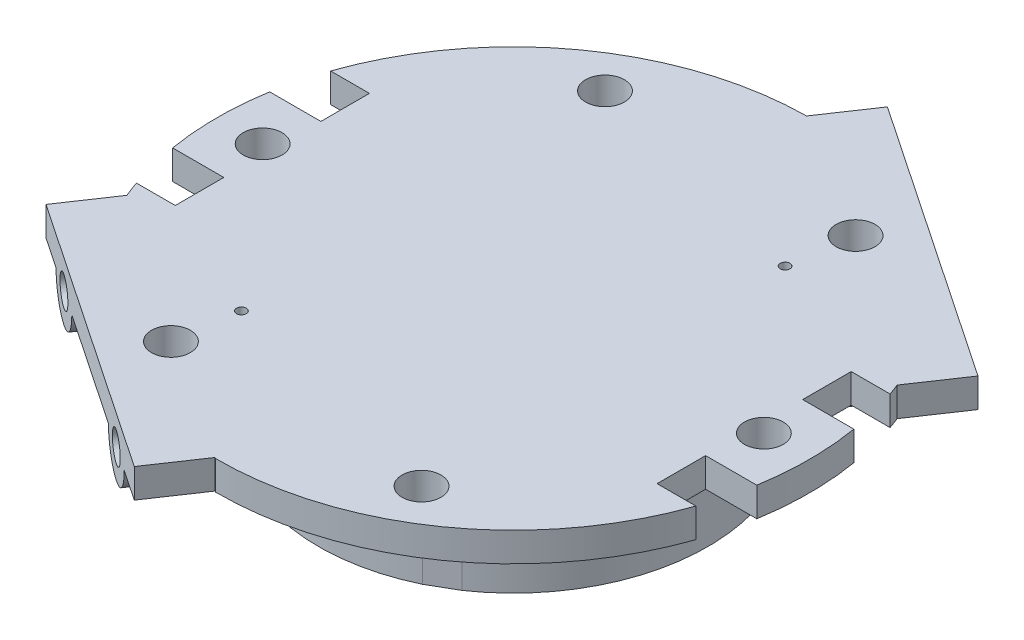
SolidWorks part; units mm, degrees
ref_plane "Alzado" through (0, 0, 0) normal (0, 0, 1) x (1, 0, 0)
ref_plane "Planta" through (0, 0, 0) normal (0, 1, 0) x (1, 0, 0)
ref_plane "Vista lateral" through (0, 0, 0) normal (1, 0, 0) x (0, 0, -1)
sketch "Croquis1" plane through (0, 0, 0) normal (0, 1, 0) x (1, 0, 0)
  circle A0 centre (0, 0) radius 30.5
extrude "Saliente-Extruir1" add sketch "Croquis1" along normal blind 3
sketch "Croquis5" plane through (0, 3, 0) normal (0, 1, 0) x (1, 0, 0)
  line L1 (28.8141, -5) -> (30.0874, -5)
  line L2 (28.8141, 5) -> (30.0874, 5)
  line L3 (-24.8141, 10) -> (-28.8141, 10)
  line L4 (24.8141, -5) -> (24.8141, -10)
  line L5 (-24.8141, -10) -> (-28.8141, -10)
  line L6 (24.8141, -5) -> (28.8141, -5)
  line L7 (24.8141, 5) -> (24.8141, 10)
  line L8 (-24.8141, 5) -> (-28.8141, 5)
  line L9 (-24.8141, 5) -> (-24.8141, 10)
  line L10 (-24.8141, -5) -> (-28.8141, -5)
  line L11 (-24.8141, -5) -> (-24.8141, -10)
  line L12 (24.8141, 5) -> (28.8141, 5)
  line L13 (24.8141, -10) -> (28.8141, -10)
  line L14 (24.8141, 10) -> (28.8141, 10)
  line L15 (-28.8141, 5) -> (-30.0874, 5)
  line L16 (-28.8141, -5) -> (-30.0874, -5)
  line L18 (-24.8141, 0) -> (-12.407, -21.4896)
  line L19 (-12.407, -21.4896) -> (12.407, -21.4896)
  line L20 (12.407, -21.4896) -> (24.8141, 0)
  line L21 (24.8141, 0) -> (12.407, 21.4896)
  line L22 (12.407, 21.4896) -> (-12.407, 21.4896)
  line L23 (-12.407, 21.4896) -> (-24.8141, 0)
  circle A0 centre (0, 0) radius 21.4896 construction
  circle A1 centre (0, 0) radius 30.5 construction
  arc A2 (-28.8141, 10) -> (-30.0874, 5) centre (0, 0) ccw
  arc A4 (-30.0874, -5) -> (-28.8141, -10) centre (0, 0) ccw
  arc A5 (30.0874, -5) -> (28.8141, -10) centre (0, 0) cw
  arc A6 (28.8141, 10) -> (30.0874, 5) centre (0, 0) cw
  circle M2 centre (0, 0) radius 30.5
extrude "Cortar-Extruir3" cut sketch "Croquis5" against normal blind 4 contours L10 L16 L5 L11 M2 | L15 L8 L9 L3 M2 | L14 L7 L12 L2 M2 | L4 L13 L1 L6 M2 region at (27.1844, 3, 7.3876) region at (-27.1844, 3, 7.3876) region at (27.1844, 3, -7.3876) region at (-27.1844, 3, -7.3876)
sketch "Croquis7" plane through (0, 3, 0) normal (0, 1, 0) x (1, 0, 0)
  line L2 (25.8141, 0) -> (12.907, 22.3556)
  line L3 (12.907, 22.3556) -> (-12.907, 22.3556)
  line L4 (-12.907, 22.3556) -> (-25.8141, 0)
  line L5 (-25.8141, 0) -> (-12.907, -22.3556)
  line L6 (-12.907, -22.3556) -> (12.907, -22.3556)
  line L7 (12.907, -22.3556) -> (25.8141, 0)
  circle A0 centre (25.8141, 0) radius 2
  circle A4 centre (-25.8141, 0) radius 2
  circle A5 centre (0, 0) radius 22.3556 construction
  circle A6 centre (12.907, 22.3556) radius 2
  circle A7 centre (-12.907, -22.3556) radius 2
  circle A8 centre (-12.907, 22.3556) radius 2
  circle A9 centre (12.907, -22.3556) radius 2
extrude "Cortar-Extruir4" cut sketch "Croquis7" against normal blind 10 contours A8 L4 L3 | A4 L4 L5 | A4 L5 L4 | A8 L3 L4 | L2 A6 L3 | L3 A6 L2 | L7 A0 L2 | L2 A0 L7 | A7 L5 L6 | A7 L6 L5 | L6 A9 L7 | L7 A9 L6 | A4 region at (24.7114, 3, 0) region at (26.3654, 3, 0) region at (12.3557, 3, -21.4007) region at (13.1827, 3, -22.8331) region at (13.1827, 3, 22.8331) region at (12.3557, 3, 21.4007) region at (-12.3557, 3, -21.4007) region at (-13.1827, 3, -22.8331) region at (-13.1827, 3, 22.8331) region at (-12.3557, 3, 21.4007) region at (-24.7114, 3, 0) region at (-26.3654, 3, 0)
sketch "Croquis8" plane through (0, 3, 0) normal (0, 1, 0) x (1, 0, 0)
  line L0 (0, 0) -> (12, 0)
  line L1 (12, 0) -> (12, 16)
  line L2 (0, 0) -> (-12, 0)
  line L3 (-12, 0) -> (-12, -16)
  circle A0 centre (12, 16) radius 0.5
  circle A1 centre (-12, -16) radius 0.5
extrude "Cortar-Extruir5" cut sketch "Croquis8" against normal blind 3 contours A1 | A0 region at (11.6564, 3, -16.3436) region at (-11.6564, 3, 15.6564)
sketch "Croquis9" plane through (0, 3, 0) normal (0, 1, 0) x (1, 0, 0)
  line L2 (-10, 17.3205) -> (-8.701, 18.0705)
  line L5 (25.6318, 16.5306) -> (27.1318, 13.9325)
  line L6 (-10, 17.3205) -> (-11.299, 16.5705)
  line L8 (10, -17.3205) -> (8.701, -18.0705)
  line L9 (10, -17.3205) -> (11.299, -16.5705)
  circle A0 centre (0, 0) radius 20.0562
  circle A1 centre (-12, -16) radius 3
  circle A2 centre (12, 16) radius 3
extrude "Saliente-Extruir2" add sketch "Croquis9" against normal blind 13 contours L2 L6 | L8 L9 region at (0, 3, 0)
sketch "Croquis11" plane through (14.0495, 0, -20.8293) normal (0.5592, 0, -0.829) x (-0.829, 0, -0.5592)
  line L1 (17.2916, 0) -> (-17.2916, 0)
  line L2 (17.2916, 0) -> (17.2916, 3)
  line L3 (17.2916, 3) -> (-17.2916, 3)
  line L4 (-17.2916, 0) -> (-17.2916, 3)
extrude "Saliente-Extruir3" add sketch "Croquis11" along normal blind 6
sketch "Croquis12" plane through (0, 3, 0) normal (0, 1, 0) x (1, 0, 0)
  circle A0 centre (12.907, 22.3556) radius 2
extrude "Cortar-Extruir7" cut sketch "Croquis12" against normal blind 3
sketch "Croquis13" plane through (17.4047, 0, -25.8035) normal (0.5592, 0, -0.829) x (-0.829, 0, -0.5592)
  line L0 (-17.2916, 0) -> (17.2916, 0)
  line L1 (17.2916, 3) -> (-17.2916, 3)
  line L2 (17.2916, 3) -> (-17.2916, 3) construction
  line L3 (17.2916, 0) -> (17.2916, 3) construction
  circle A1 centre (10, 0) radius 3
  circle A2 centre (-10, 0) radius 3
  circle A3 centre (10, 0) radius 1.5
  circle A5 centre (-10, 0) radius 1.5
  line M4 (-17.2916, 0) -> (17.2916, 0)
extrude "Saliente-Extruir4" add sketch "Croquis13" against normal blind 20 contours A3 L0 A1 | A3 L0 A1 | A5 L0 A2 | A5 L0 A2 | A5 M4 | A3 M4 region at (25.6951, 1.5671, -20.2116) region at (25.6951, -0.6366, -20.2116) region at (23.8297, -0.0671, -21.4698) region at (10.8337, 2.0739, -30.2358) region at (10.9797, -0.0671, -30.1373) region at (9.1143, -0.6366, -31.3955)
sketch "Croquis14" plane through (17.4047, 0, -25.8035) normal (0.5592, 0, -0.829) x (-0.829, 0, -0.5592)
  circle A0 centre (-10, 0) radius 1.5
  circle A1 centre (10, 0) radius 1.5
extrude "Cortar-Extruir8" cut sketch "Croquis14" against normal blind 6
sketch "Croquis15" plane through (0, 3, 0) normal (0, 1, 0) x (1, 0, 0)
  line L0 (28.3849, 11.16) -> (-0.2859, 30.4987)
  line L1 (28.3849, 11.16) -> (0.1409, -30.7136)
  line L2 (-0.2859, 30.4987) -> (-28.5299, -11.3749)
  line L3 (0.1409, -30.7136) -> (-28.5299, -11.3749)
  circle A0 centre (-0.2859, 0) radius 30.7165
  arc M12 (-28.8141, -10) -> (28.8141, -10) centre (0, 0) ccw
  circle M28 centre (-12.907, -22.3556) radius 2
extrude "Cortar-Extruir9" cut sketch "Croquis15" against normal blind 3 contours L3 M12 M28 region at (-15.494, 3, 22.7434)
sketch "Croquis16" plane through (-14.1945, 0, 21.0442) normal (-0.5592, 0, 0.829) x (0.829, 0, 0.5592)
  line L0 (-16.9088, 0) -> (-16.9088, 3)
  line L1 (-16.9088, 0) -> (16.78, 0)
  line L2 (-16.9088, 3) -> (16.78, 3)
  line L3 (16.78, 0) -> (16.78, 3)
extrude "Saliente-Extruir5" add sketch "Croquis16" along normal blind 6
sketch "Croquis17" plane through (0, 3, 0) normal (0, 1, 0) x (1, 0, 0)
  circle A0 centre (-12.907, -22.3556) radius 2
extrude "Cortar-Extruir10" cut sketch "Croquis17" against normal blind 3
sketch "Croquis18" plane through (-17.5497, 0, 26.0185) normal (-0.5592, 0, 0.829) x (0.829, 0, 0.5592)
  line L2 (-16.9088, 0) -> (16.78, 0) construction
  circle A0 centre (9.9356, 0) radius 3
  circle A1 centre (-10.0644, 0) radius 3
extrude "Saliente-Extruir6" add sketch "Croquis18" against normal blind 25
sketch "Croquis19" plane through (-17.5497, 0, 26.0185) normal (-0.5592, 0, 0.829) x (0.829, 0, 0.5592)
  circle A0 centre (-10.0644, 0) radius 1.5
  circle A1 centre (9.9356, 0) radius 1.5
extrude "Cortar-Extruir11" cut sketch "Croquis19" against normal blind 5
